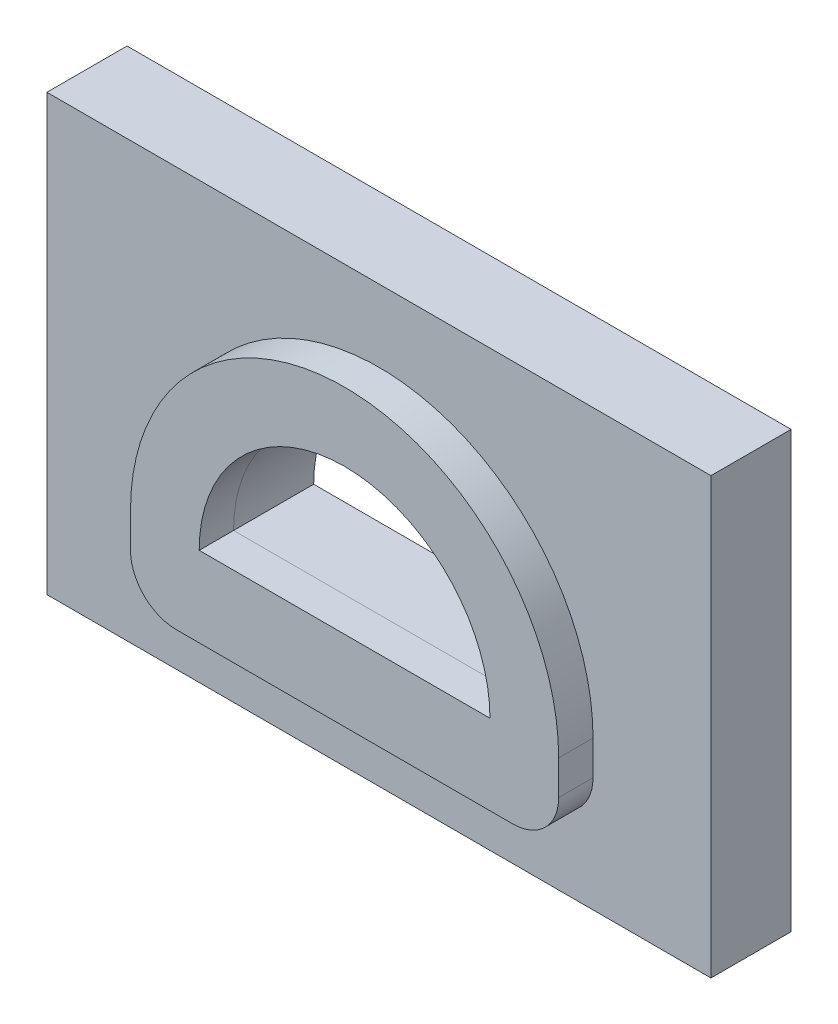
SolidWorks part; units mm, degrees
ref_plane "Front Plane" through (0, 0, 0) normal (0, 0, 1) x (1, 0, 0)
ref_plane "Top Plane" through (0, 0, 0) normal (0, 1, 0) x (1, 0, 0)
ref_plane "Right Plane" through (0, 0, 0) normal (1, 0, 0) x (0, 0, -1)
sketch "Sketch1" plane through (0, 0, 0) normal (0, 0, 1) x (1, 0, 0)
  line L0 (-4.2, 0) -> (8.5, 0)
  line L1 (-7.2, 0) -> (-7.2, -3.5)
  line L2 (-7.2, -3.5) -> (11.5, -3.5)
  line L3 (11.5, -3.5) -> (11.5, 0)
  line L5 (-12.35, 12.5) -> (16.65, 12.5)
  line L6 (-12.35, 12.5) -> (-12.35, -6.5)
  line L7 (-12.35, -6.5) -> (16.65, -6.5)
  line L8 (16.65, 12.5) -> (16.65, -6.5)
  arc A0 (8.5, 0) -> (-4.2, 0) centre (2.15, 0) ccw
  arc A1 (11.5, 0) -> (-7.2, 0) centre (2.15, 0) ccw
  point P2 (2.15, -6.5)
  dimension "D1" = 12.7
  dimension "D3" = 3.5
  dimension "D4" = 29
  dimension "D5" = 6.5
  dimension "D7" = 19
  dimension "D2" = 3
extrude "cap alignment lip" add sketch "Sketch1" along normal blind 1.5 contours L3 A1 L1 L2 A0 L0 region at (2.15, 9.1231, 0)
extrude "cap body" add sketch "Sketch1<3>" against normal blind 3.5 separate body contours L8 L5 L6 L7 A1 L3 L2 L1 | L3 A1 L1 L2 A0 L0 region at (2.15, 9.1231, 0) region at (2.15, 12.1533, 0)
sketch "Sketch1<3>" plane through (0, 0, 0) normal (0, 0, 1) x (1, 0, 0) same geometry as "Sketch1"
fillet "lip corner fillet" radius 2 2 edges at (-7.2, -3.5, 0.75) (11.5, -3.5, 0.75)
